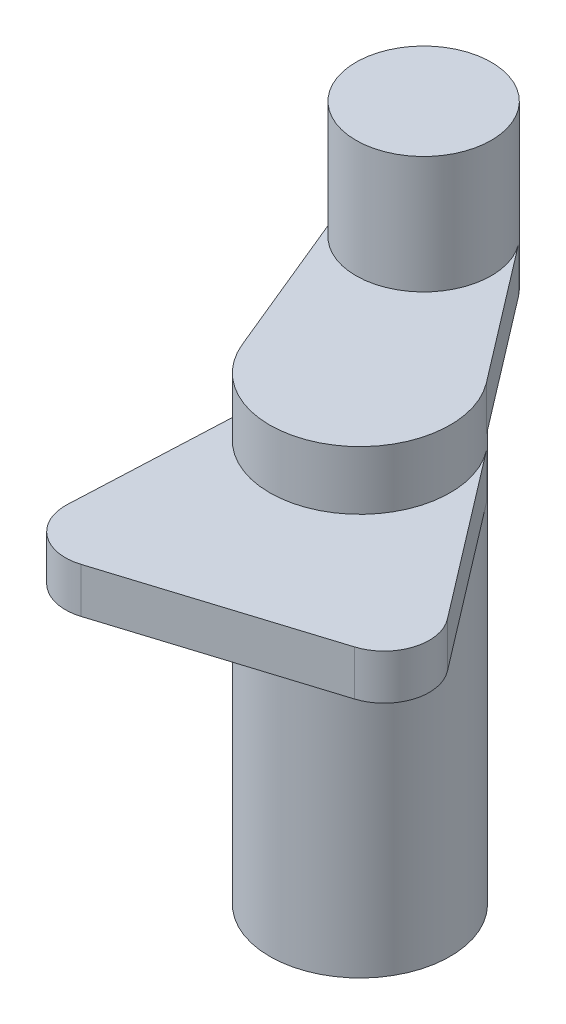
SolidWorks part; units mm, degrees
note: The reader was unsure of these and kept them because the rebuilt part matched: shared geometry of "Sketch2<3>".
ref_plane "Front Plane" through (0, 0, 0) normal (0, 0, 1) x (1, 0, 0)
ref_plane "Top Plane" through (0, 0, 0) normal (0, 1, 0) x (1, 0, 0)
ref_plane "Right Plane" through (0, 0, 0) normal (1, 0, 0) x (0, 0, -1)
sketch "Sketch1" plane through (0, 0, 0) normal (0, 1, 0) x (1, 0, 0)
  circle A0 centre (0, 0) radius 20
  dimension "D1" = 40
extrude "Boss-Extrude1" add sketch "Sketch1" along normal mid plane 102
sketch "Sketch2" plane through (0, 51, 0) normal (0, 1, 0) x (1, 0, 0)
  line L0 (-7.1748, 42.3191) -> (15.8895, 12.1459)
  line L1 (-32.9607, 27.4951) -> (-18.4917, -7.6195)
  line L2 (0, 0) -> (-19.0919, 33.2097) construction
  circle A0 centre (-19.0919, 33.2097) radius 15
  circle A1 centre (0, 0) radius 20
  circle A2 centre (0, 0) radius 20
  dimension "D2" = 30
  dimension "D3" = 15
  dimension "D1" = 0
extrude "Boss-Extrude2" add sketch "Sketch2" against normal blind 10
extrude "Boss-Extrude3" add sketch "Sketch2<3>" along normal blind 26
sketch "Sketch2<3>" plane through (0, 51, 0) normal (0, 1, 0) x (1, 0, 0) same geometry as "Sketch2"
ref_plane "Plane1" through (0, 28, 0) normal (0, -1, 0) x (-1, 0, 0)
sketch "Sketch3" plane through (0, 28, 0) normal (0, -1, 0) x (-1, 0, 0)
  line L0 (18.4917, -7.6195) -> (20.1772, -44.6536)
  line L1 (7.1981, -54.651) -> (-38.9954, -40.18)
  line L2 (-43.9507, -24.5643) -> (-15.8895, 12.1459)
  line L3 (32.9607, 27.4951) -> (18.4917, -7.6195) construction
  arc A0 (20.1772, -44.6536) -> (7.1981, -54.651) centre (10.1875, -45.1083) cw
  arc A1 (-38.9954, -40.18) -> (-43.9507, -24.5643) centre (-36.0059, -30.6373) cw
  arc A2 (-15.8895, 12.1459) -> (18.4917, -7.6195) centre (0, 0) ccw construction
  arc A3 (-15.8895, 12.1459) -> (18.4917, -7.6195) centre (0, 0) ccw
  dimension "D1" = 70
  dimension "D3" = 10
  dimension "D2" = 70
  dimension "D4" = 50
  dimension "D5" = 155
extrude "Boss-Extrude4" add sketch "Sketch3" against normal blind 10
